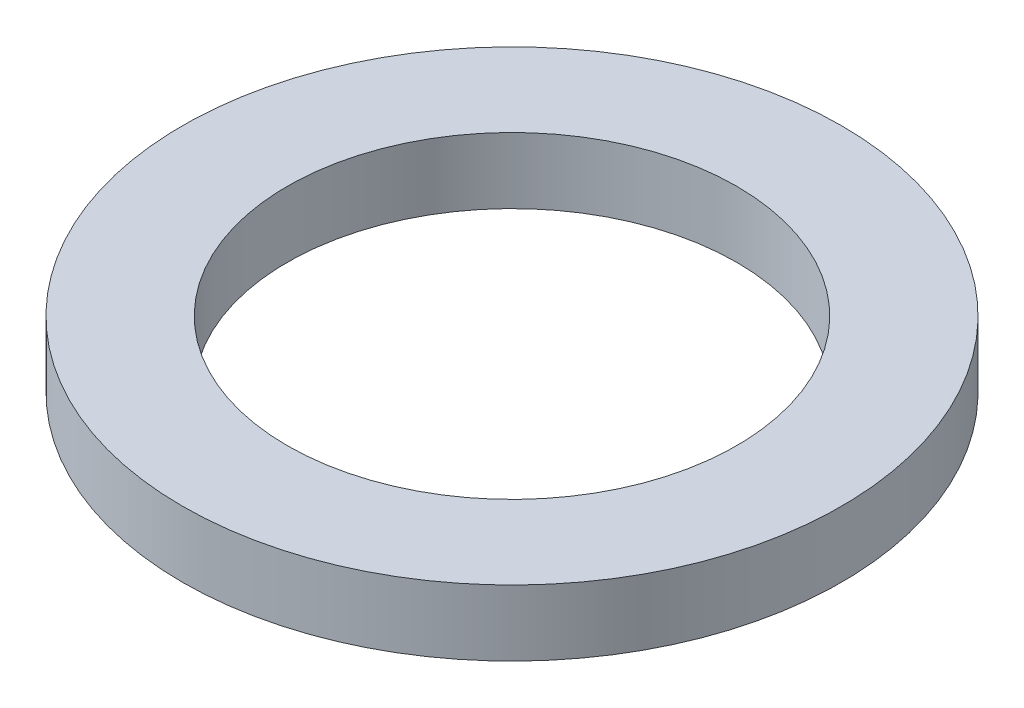
SolidWorks part; units mm, degrees
ref_plane "Front Plane" through (0, 0, 0) normal (0, 0, 1) x (1, 0, 0)
ref_plane "Top Plane" through (0, 0, 0) normal (0, 1, 0) x (1, 0, 0)
ref_plane "Right Plane" through (0, 0, 0) normal (1, 0, 0) x (0, 0, -1)
sketch "Sketch1" plane through (0, 0, 0) normal (0, 1, 0) x (1, 0, 0)
  circle A0 centre (0, 0) radius 55
  dimension "FLANGE_OD" = 110
extrude "Boss-Extrude1" add sketch "Sketch1" along normal blind 11
sketch "Sketch2" plane through (0, 0, 0) normal (0, 1, 0) x (1, 0, 0)
  circle A0 centre (0, 0) radius 37.5
  dimension "BORE_D" = 75
extrude "Cut-Extrude1" cut sketch "Sketch2" along normal through all
sketch "Sketch3" plane through (0, 11, 0) normal (0, 1, 0) x (1, 0, 0)
  circle A0 centre (0, 0) radius 21.1365 construction
  circle A1 centre (-21.1365, 0) radius 2.2593
  dimension "BOLT_D" = 4.5186
  dimension "BOLT_PCD" = 42.2729
extrude "Cut-Extrude2" cut sketch "Sketch3" against normal blind 9.4766 rebuild error yes
pattern_circular "CirPattern1" count 4 over 360 rebuild error yes
